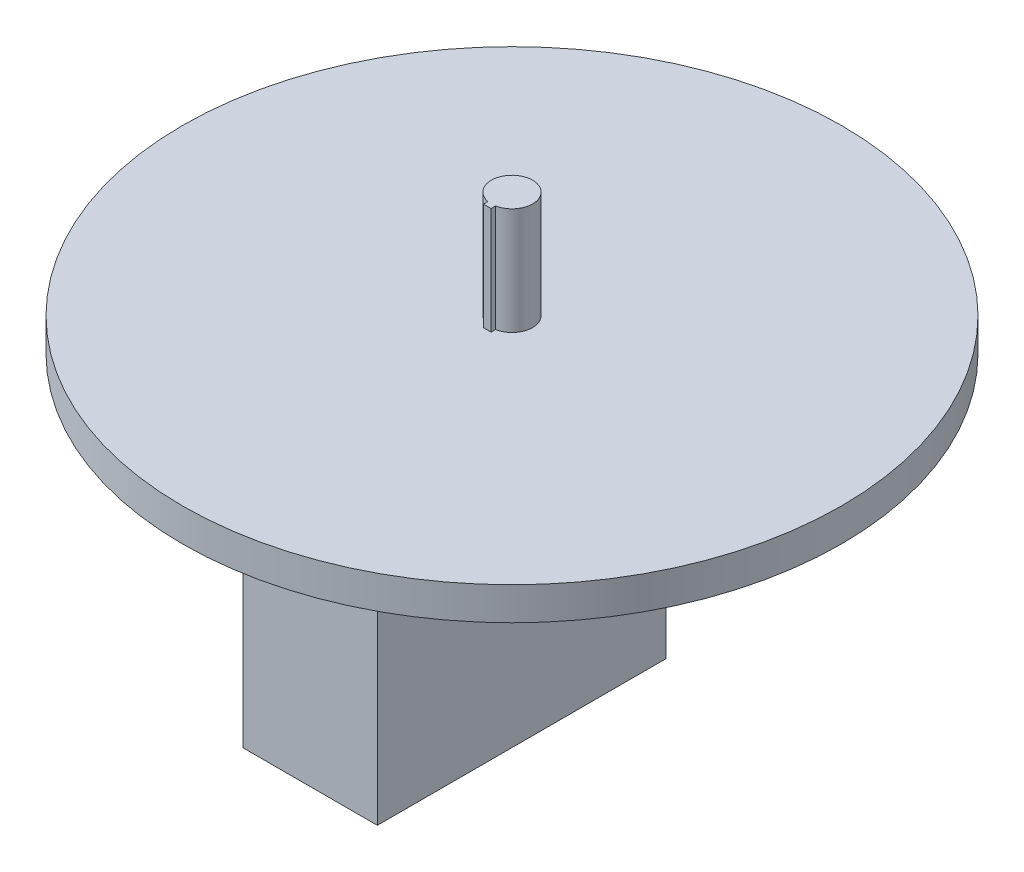
SolidWorks part; units mm, degrees
ref_plane "Front Plane" through (0, 0, 0) normal (0, 0, 1) x (1, 0, 0)
ref_plane "Top Plane" through (0, 0, 0) normal (0, 1, 0) x (1, 0, 0)
ref_plane "Right Plane" through (0, 0, 0) normal (1, 0, 0) x (0, 0, -1)
sketch "Sketch1" plane through (0, 0, 0) normal (0, 1, 0) x (1, 0, 0)
  circle A0 centre (0, 0) radius 400
  dimension "D1" = 800
extrude "Boss-Extrude1" add sketch "Sketch1" along normal blind 10
sketch "Sketch3" plane through (0, 10, 0) normal (0, 1, 0) x (1, 0, 0)
  line L5 (-4.6, -30.015) -> (4.6, -30.015)
  line L6 (-4.6, -30.015) -> (-4.6, -24.5732)
  line L8 (4.6, -30.015) -> (4.6, -24.5732)
  line L9 (-4.6, -30.015) -> (0, -25) construction
  line L10 (0, -25) -> (4.6, -30.015) construction
  arc A0 (4.6, -24.5732) -> (-4.6, -24.5732) centre (0, 0) ccw
  point P3 (0, -25)
  dimension "D1" = 50
extrude "Boss-Extrude5" add sketch "Sketch3" along normal blind 130
extrude "Boss-Extrude6" add sketch "Sketch1<4>" against normal blind 30
sketch "Sketch1<4>" plane through (0, 0, 0) normal (0, 1, 0) x (1, 0, 0) same geometry as "Sketch1"
sketch "Sketch4" plane through (0, -30, 0) normal (0, -1, 0) x (1, 0, 0)
  line L1 (-198.8631, 127.5196) -> (-35.9526, 127.5196)
  line L2 (-198.8631, 127.5196) -> (-198.8631, -223.0188)
  line L3 (-198.8631, -223.0188) -> (-35.9526, -223.0188)
  line L4 (-35.9526, 127.5196) -> (-35.9526, -223.0188)
extrude "Boss-Extrude7" add sketch "Sketch4" along normal blind 450
